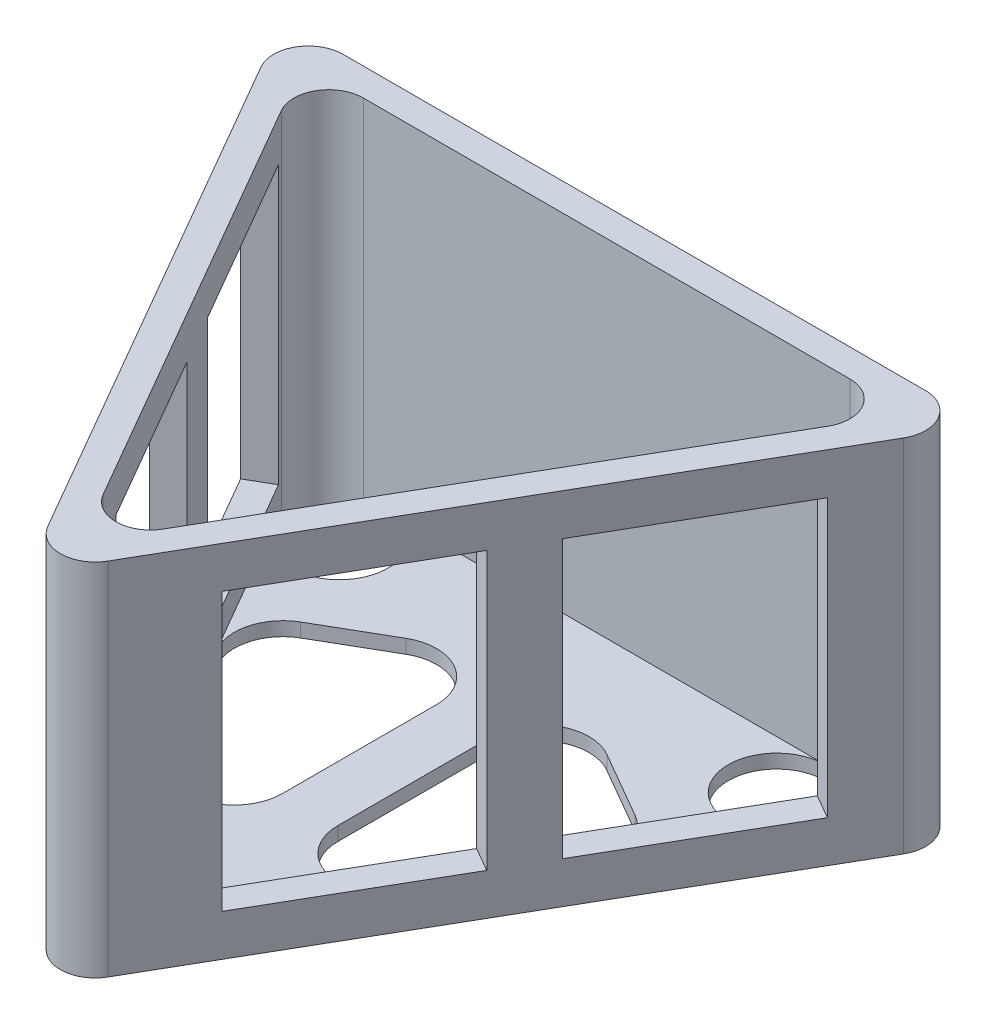
SolidWorks part; units mm, degrees
ref_plane "Front Plane" through (0, 0, 0) normal (0, 0, 1) x (1, 0, 0)
ref_plane "Top Plane" through (0, 0, 0) normal (0, 1, 0) x (1, 0, 0)
ref_plane "Right Plane" through (0, 0, 0) normal (1, 0, 0) x (0, 0, -1)
sketch "Sketch1" plane through (0, 0, 0) normal (0, 1, 0) x (1, 0, 0)
  line L0 (-55.0808, 36.1982) -> (-4.3714, 36.1982)
  line L1 (-4.3714, 36.1982) -> (-29.7261, -7.7174)
  line L2 (-55.0808, 36.1982) -> (-29.7261, -7.7174)
  line L3 (-51.6167, 34.1982) -> (-7.8355, 34.1982)
  line L4 (-7.8355, 34.1982) -> (-29.7261, -3.7174)
  line L5 (-51.6167, 34.1982) -> (-29.7261, -3.7174)
  dimension "D1" = 2
  dimension "D2" = 50.7094
extrude "Boss-Extrude1" add sketch "Sketch1" along normal blind 26
fillet "Fillet1" radius 2.5 6 edges at (-29.7261, 13, 3.7174) (-29.7261, 13, 7.7174) (-4.3714, 13, -36.1982) (-7.8355, 13, -34.1982) (-51.6167, 13, -34.1982) (-55.0808, 13, -36.1982)
sketch "Sketch2" plane through (-25.6363, 0, 14.8011) normal (-0.866, 0, 0.5) x (0.5, 0, 0.866)
  line L0 (-54.5588, 26) -> (-12.5097, 0) construction
  line L1 (-12.5097, 26) -> (-54.5588, 0) construction
  line L2 (-33.5343, 13) -> (-25.5343, 13) construction
  line L8 (-33.5343, 13) -> (-43.5343, 13) construction
  line L13 (-32.5343, 3) -> (-18.5343, 3)
  line L14 (-32.5343, 3) -> (-32.5343, 23)
  line L15 (-50.5343, 3) -> (-36.5343, 3)
  line L16 (-32.5343, 23) -> (-18.5343, 23)
  line L17 (-18.5343, 3) -> (-18.5343, 23)
  line L18 (-32.5343, 3) -> (-18.5343, 23) construction
  line L19 (-32.5343, 23) -> (-18.5343, 3) construction
  line L20 (-50.5343, 3) -> (-50.5343, 23)
  line L21 (-50.5343, 23) -> (-36.5343, 23)
  line L22 (-36.5343, 3) -> (-36.5343, 23)
  line L23 (-50.5343, 3) -> (-36.5343, 23) construction
  line L24 (-50.5343, 23) -> (-36.5343, 3) construction
  dimension "D3" = 8
  dimension "D1" = 14
  dimension "D2" = 20
  dimension "D4" = 10
  dimension "D5" = 14
  dimension "D6" = 20
extrude "Cut-Extrude1" cut sketch "Sketch2" against normal up to next contours L13 L17 L16 L14 | L15 L22 L21 L20 region at (-38.4034, 13, -7.3122) region at (-47.4034, 13, -22.9006)
sketch "Sketch3" plane through (-18.9528, 0, -10.9424) normal (0.866, 0, 0.5) x (0.5, 0, -0.866)
  line L0 (-17.2164, 26) -> (24.8327, 0) construction
  line L1 (-17.2164, 0) -> (24.8327, 26) construction
  line L2 (3.8082, 13) -> (13.8082, 13) construction
  line L9 (-11.1918, 3) -> (2.8082, 3)
  line L13 (3.8082, 13) -> (-4.1918, 13) construction
  line L14 (-11.1918, 3) -> (-11.1918, 23)
  line L15 (-11.1918, 23) -> (2.8082, 23)
  line L16 (6.8082, 3) -> (20.8082, 3)
  line L21 (6.8082, 3) -> (6.8082, 23)
  line L22 (6.8082, 23) -> (20.8082, 23)
  line L23 (20.8082, 3) -> (20.8082, 23)
  line L24 (6.8082, 3) -> (20.8082, 23) construction
  line L25 (6.8082, 23) -> (20.8082, 3) construction
  line L26 (2.8082, 3) -> (2.8082, 23)
  line L27 (-11.1918, 3) -> (2.8082, 23) construction
  line L28 (-11.1918, 23) -> (2.8082, 3) construction
  dimension "D3" = 10
  dimension "D1" = 14
  dimension "D2" = 20
  dimension "D4" = 8
  dimension "D5" = 14
  dimension "D6" = 20
extrude "Cut-Extrude2" cut sketch "Sketch3" against normal up to next contours L9 L26 L15 L14 | L16 L23 L22 L21
sketch "Sketch5" plane through (0, 0, 0) normal (0, -1, 0) x (1, 0, 0)
  line L6 (-29.7261, -34.1982) -> (-29.7261, -33.4595)
  line L15 (-30.7261, -35.1915) -> (-49.2735, -24.4832) construction
  line L16 (-12.1656, -34.1982) -> (-47.2866, -34.1982) construction
  line L17 (-31.7261, -34.1982) -> (-31.7261, -33.4595) construction
  line L18 (-29.7261, -33.4595) -> (-45.8242, -24.1653)
  line L19 (-30.7261, -31.7274) -> (-9.4606, -19.4498) construction
  line L24 (-29.7261, -33.4595) -> (-13.628, -24.1653)
  line L25 (-31.7261, -29.9954) -> (-44.8242, -22.4332)
  line L26 (-27.7261, -34.6142) -> (-12.628, -25.8973)
  line L27 (-27.7261, -34.1982) -> (-27.7261, -34.6142)
  line L28 (-31.7261, -34.6142) -> (-46.8242, -25.8973)
  line L32 (-27.7261, -29.9954) -> (-14.628, -22.4332)
  line L33 (-31.7261, -34.1982) -> (-31.7261, -34.6142)
  line L34 (-49.4516, -30.4482) -> (-31.8912, -0.0326)
  line L35 (-27.561, -0.0326) -> (-10.0006, -30.4482)
  line L36 (-12.1656, -34.1982) -> (-47.2866, -34.1982)
  line L37 (-28.7261, -31.7274) -> (-47.2735, -21.0191) construction
  line L38 (-28.7261, -35.1915) -> (-7.4606, -22.9139) construction
  line L39 (-27.7261, -34.1982) -> (-27.7261, -33.4595) construction
  line L40 (-29.7261, -33.4595) -> (-8.4606, -21.1819) construction
  line L41 (-29.7261, -33.4595) -> (-48.2735, -22.7511) construction
  line L42 (-29.7261, -33.4595) -> (-29.7261, 1.2174)
  line L43 (-27.7261, -29.9954) -> (-27.7261, 0.2174)
  line L44 (-31.7261, -29.9954) -> (-31.7261, 0.2174)
  line L45 (-31.7261, -33.4595) -> (-31.7261, 1.2174) construction
  line L46 (-27.7261, -33.4595) -> (-27.7261, 1.2174) construction
  arc A2 (-27.561, -0.0326) -> (-31.8912, -0.0326) centre (-29.7261, -1.2826) ccw construction
  arc A3 (-27.561, -0.0326) -> (-31.8912, -0.0326) centre (-29.7261, -1.2826) ccw
  line M22 (-27.561, -0.0326) -> (-10.0006, -30.4482)
  line M24 (-12.1656, -34.1982) -> (-47.2866, -34.1982)
  line M26 (-49.4516, -30.4482) -> (-31.8912, -0.0326)
  arc M27 (-31.8912, -0.0326) -> (-27.561, -0.0326) centre (-29.7261, -1.2826) cw
  dimension "D3" = 2
  dimension "D1" = 2
  dimension "D2" = 2
  dimension "D4" = 2
extrude "Boss-Extrude2" add sketch "Sketch5" against normal blind 1 contours L18 L28 L33 L6 M26 M24 | L42 L44 L25 L18 M27 M26 | L24 L32 L43 L42 M22 M27 | L6 L27 L26 L24 M24 M22 region at (-38.4641, 0, -29.5443) region at (-20.9881, 0, -29.5443) region at (-29.3438, 0, -16.121) region at (-37.584, 0, -28.4813)
fillet "Fillet3" radius 3.5 10 edges at (-12.628, 0.5, -25.8973) (-14.628, 0.5, -22.4332) (-44.8242, 0.5, -22.4332) (-46.8242, 0.5, -25.8973) (-31.7261, 0.5, 0.2174) (-27.7261, 0.5, 0.2174) (-27.7261, 0.5, -29.9954) (-31.7261, 0.5, -29.9954) (-27.0056, 0.5, -34.1982) (-32.4466, 0.5, -34.1982)
